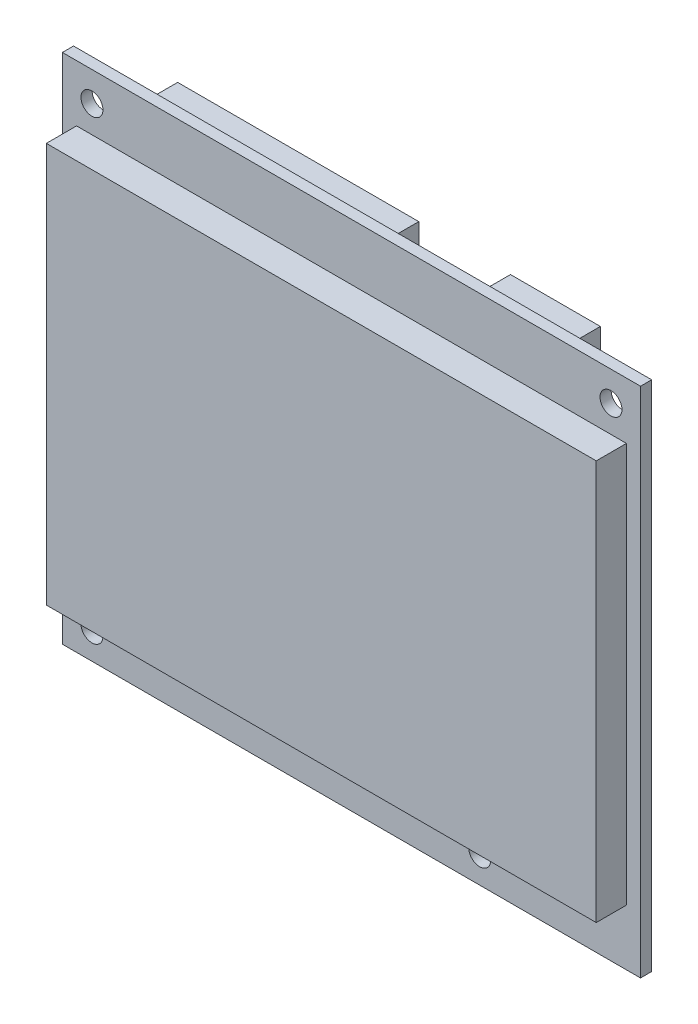
SolidWorks part; units mm, degrees
ref_plane "Front Plane" through (0, 0, 0) normal (0, 0, 1) x (1, 0, 0)
ref_plane "Top Plane" through (0, 0, 0) normal (0, 1, 0) x (1, 0, 0)
ref_plane "Right Plane" through (0, 0, 0) normal (1, 0, 0) x (0, 0, -1)
sketch "Sketch1" plane through (0, 0, 0) normal (0, 0, -1) x (-1, 0, 0)
  line L1 (-32.25, -24.25) -> (32.25, -24.25) construction
  line L2 (-32.25, -24.25) -> (-32.25, 24.25) construction
  line L3 (-32.25, 24.25) -> (32.25, 24.25) construction
  line L4 (32.25, -24.25) -> (32.25, 24.25) construction
  line L5 (-32.25, -24.25) -> (32.25, 24.25) construction
  line L6 (-32.25, 24.25) -> (32.25, -24.25) construction
  line L7 (-36, 28) -> (41.7, 28) construction
  line L8 (-36, 28) -> (-36, -28.5) construction
  line L9 (-36, -28.5) -> (41.7, -28.5) construction
  line L10 (41.7, 28) -> (41.7, -28.5) construction
  line L11 (-37.9864, 35.9904) -> (43.7, 35.9904)
  line L12 (-37.9864, 35.9904) -> (-37.9864, -36.425)
  line L13 (-37.9864, -36.425) -> (43.7, -36.425)
  line L14 (43.7, 35.9904) -> (43.7, -36.425)
  point P0 (0, 0)
  dimension "D1" = 64.5
  dimension "D2" = 48.5
  dimension "D3" = 3.75
  dimension "D4" = 3.75
  dimension "D5" = 56.5
  dimension "D6" = 77.7
  dimension "D7" = 7.925
  dimension "D8" = 72.4154
  dimension "D9" = 81.6864
  dimension "D10" = 2
extrude "Boss-Extrude1" add sketch "Sketch1" along normal blind 1.5748
sketch "Sketch2" plane through (0, 0, 0) normal (0, 0, -1) x (-1, 0, 0)
  line L1 (-36, -28.5) -> (41.7, -28.5)
  line L2 (-36, -28.5) -> (-36, 28)
  line L3 (-36, 28) -> (41.7, 28)
  line L4 (41.7, -28.5) -> (41.7, 28)
  line L5 (41.7, 28) -> (49.6841, 28) construction
  line L6 (-36, 28) -> (-43.9841, 28) construction
  line L10 (-32.25, -24.25) -> (32.25, -24.25) construction
  line L11 (-32.25, -24.25) -> (-32.25, 24.25) construction
  line L12 (-32.25, 24.25) -> (32.25, 24.25) construction
  line L13 (32.25, -24.25) -> (32.25, 24.25) construction
  line L14 (-32.25, -24.25) -> (32.25, 24.25) construction
  line L15 (-32.25, 24.25) -> (32.25, -24.25) construction
  point P0 (0, 0)
  point P14 (0, 0)
  dimension "D1" = 56.5
  dimension "D2" = 77.7
  dimension "D3" = 3.75
  dimension "D4" = 48.5
  dimension "D5" = 64.5
  dimension "D6" = 3.75
extrude "Boss-Extrude2" add sketch "Sketch2" against normal blind 4.27
sketch "Sketch3" plane through (0, 0, -1.5748) normal (0, 0, 1) x (1, 0, 0)
  line L1 (25.66, 33.8141) -> (12.96, 33.8141)
  line L2 (25.66, 33.8141) -> (25.66, 28.7341)
  line L3 (25.66, 28.7341) -> (12.96, 28.7341)
  line L4 (12.96, 33.8141) -> (12.96, 28.7341)
  line L6 (0, 33.8141) -> (-34.0711, 33.8141)
  line L7 (0, 33.8141) -> (0, 28.7341)
  line L8 (0, 28.7341) -> (-34.0711, 28.7341)
  line L9 (-34.0711, 33.8141) -> (-34.0711, 28.7341)
  line L10 (-34.0711, -29.1593) -> (0, -29.1593)
  line L11 (-34.0711, -29.1593) -> (-34.0711, -34.2393)
  line L12 (-34.0711, -34.2393) -> (0, -34.2393)
  line L13 (0, -29.1593) -> (0, -34.2393)
  dimension "D1" = 5.08
  dimension "D2" = 12.7
sketch "Sketch4" plane through (0, 0, -1.5748) normal (0, 0, -1) x (-1, 0, 0)
  line L0 (43.7, 35.9904) -> (-37.9864, 35.9904) construction
  line L1 (-37.9864, 35.9904) -> (-37.9864, -36.425) construction
  line L2 (43.7, -36.425) -> (43.7, 35.9904) construction
  line L3 (-37.9864, -36.425) -> (43.7, -36.425) construction
  line L4 (-37.9864, 35.9904) -> (-37.9864, -36.425) construction
  circle A0 centre (39.525, 31.8154) radius 1.55
  circle A1 centre (39.525, -32.625) radius 1.55
  circle A2 centre (-15.2614, -32.625) radius 1.55
  circle A3 centre (-33.8114, 31.8154) radius 1.55
  dimension "D3" = 3.1
  dimension "D1" = 4.175
  dimension "D2" = 4.175
  dimension "D4" = 4.175
  dimension "D5" = 3.8
  dimension "D6" = 22.725
extrude "Cut-Extrude1" cut sketch "Sketch4" against normal through all
extrude "Boss-Extrude3" add sketch "Sketch3" against normal blind 5.08
sketch "Sketch5" plane through (0, 0, -1.5748) normal (0, 0, -1) x (-1, 0, 0)
  line L0 (19.4766, 13.5356) -> (30.7313, 2.2809)
  line L1 (30.7313, 2.2809) -> (19.4766, -8.9738)
  line L2 (19.4766, -8.9738) -> (8.2218, 2.2809)
  line L3 (8.2218, 2.2809) -> (19.4766, 13.5356)
  line L5 (-15.8477, -24.7973) -> (-26.991, -24.7973)
  line L6 (-15.8477, -24.7973) -> (-15.8477, -9.9767)
  line L7 (-15.8477, -9.9767) -> (-26.991, -9.9767)
  line L8 (-26.991, -24.7973) -> (-26.991, -9.9767)
extrude "Boss-Extrude4" add sketch "Sketch5" along normal blind 2
